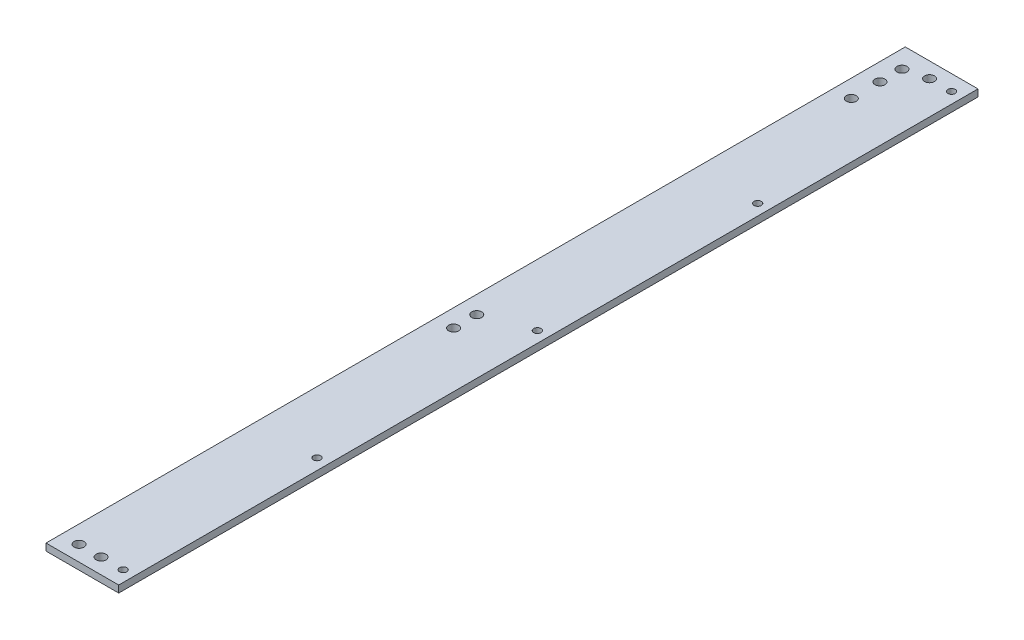
SolidWorks part; units mm, degrees
ref_plane "Front Plane" through (0, 0, 0) normal (0, 0, 1) x (1, 0, 0)
ref_plane "Top Plane" through (0, 0, 0) normal (0, 1, 0) x (1, 0, 0)
ref_plane "Right Plane" through (0, 0, 0) normal (1, 0, 0) x (0, 0, -1)
sketch "Sketch1" plane through (0, 0, 0) normal (0, 1, 0) x (1, 0, 0)
  line L1 (-16.5, -195) -> (16.5, -195)
  line L2 (-16.5, -195) -> (-16.5, 195)
  line L3 (-16.5, 195) -> (16.5, 195)
  line L4 (16.5, -195) -> (16.5, 195)
  line L5 (-16.5, -195) -> (16.5, 195) construction
  line L6 (-16.5, 195) -> (16.5, -195) construction
  point P0 (0, 0)
  dimension "D1" = 33
  dimension "D2" = 390
extrude "Boss-Extrude1" add sketch "Sketch1" along normal blind 3.175
hole_wizard "M4 Clearance Hole1" positions "Sketch4" profile "Sketch5" hole size "M4" standard "ANSI Metric" end condition through all
sketch "Sketch4" plane through (0, 3.175, 0) normal (0, 1, 0) x (1, 0, 0)
  line L4 (16.5, -195) -> (16.5, 195) construction
  line L5 (16.5, 195) -> (-16.5, 195) construction
  line L6 (-8.5, 185.5) -> (-8.5, 175.5)
  line L8 (-16.5, 195) -> (-16.5, -195) construction
  line L9 (-8.5, 162.5) -> (-8.5, -7.5)
  line L11 (-8.5, -18) -> (-8.5, -188)
  line L12 (-16.5, -195) -> (16.5, -195) construction
  line L13 (-55, 0) -> (55, 0) construction
  point P9 (1.5, 188)
  point P16 (-8.5, 185.5)
  point P17 (-8.5, 175.5)
  point P27 (-8.5, 162.5)
  point P28 (-8.5, -7.5)
  point P32 (-8.5, -18)
  point P33 (-8.5, -188)
  point P52 (1.5, -188)
  dimension "D1" = 15
  dimension "D2" = 7
  dimension "D3" = 10
  dimension "D4" = 9.5
  dimension "D5" = 8
  dimension "D6" = 170
  dimension "D7" = 13
  dimension "D8" = 10.5
  dimension "D9" = 170
  dimension "D10" = 7
sketch "Sketch5" plane through (1.5, 3.175, -188) normal (1, 0, 0) x (0, 0, 1)
  line L0 (0, 0) -> (0, 3.175)
  line L1 (0, 3.175) -> (2.25, 3.175)
  line L2 (2.25, 3.175) -> (2.25, 0)
  line L5 (2.25, 0) -> (0, 0)
  line L11 (0, -6.35) -> (0, 107.95) construction
  dimension "Thru Hole Dia." = 4.5
  dimension "Thru Hole Depth" = 3.175
hole_wizard "M4x0.7 Tapped Hole1" positions "Sketch6" profile "Sketch8" tap size "M4x0.7" standard "ANSI Metric" end condition through all
sketch "Sketch6" plane through (0, 3.175, 0) normal (0, 1, 0) x (1, 0, 0)
  line L0 (16.5, -195) -> (16.5, 195) construction
  line L1 (16.5, 195) -> (-16.5, 195) construction
  line L2 (-55, 0) -> (55, 0) construction
  line L3 (11.5, 100) -> (11.5, -100)
  point P0 (11.5, 188)
  point P9 (11.5, -188)
  point P11 (11.5, 100)
  point P12 (11.5, -100)
  point P20 (11.5, 0)
  dimension "D1" = 5
  dimension "D2" = 7
  dimension "D3" = 200
  dimension "D4" = 5
sketch "Sketch8" plane through (11.5, 3.175, -188) normal (1, 0, 0) x (0, 0, 1)
  line L0 (0, 0) -> (0, 3.175)
  line L1 (0, 3.175) -> (1.65, 3.175)
  line L2 (1.65, 3.175) -> (1.65, 0)
  line L5 (1.65, 0) -> (0, 0)
  line L11 (0, -6.35) -> (0, 107.95) construction
  dimension "Thru Tap Drill Dia." = 3.3
  dimension "Thru Tap Drill Depth" = 3.175
cosmetic thread "Hole Thread1" parameters "D2"=4
cosmetic thread "Hole Thread2" parameters "D2"=4
cosmetic thread "Hole Thread3" parameters "D2"=4
cosmetic thread "Hole Thread4" parameters "D2"=4
cosmetic thread "Hole Thread5" parameters "D2"=4
